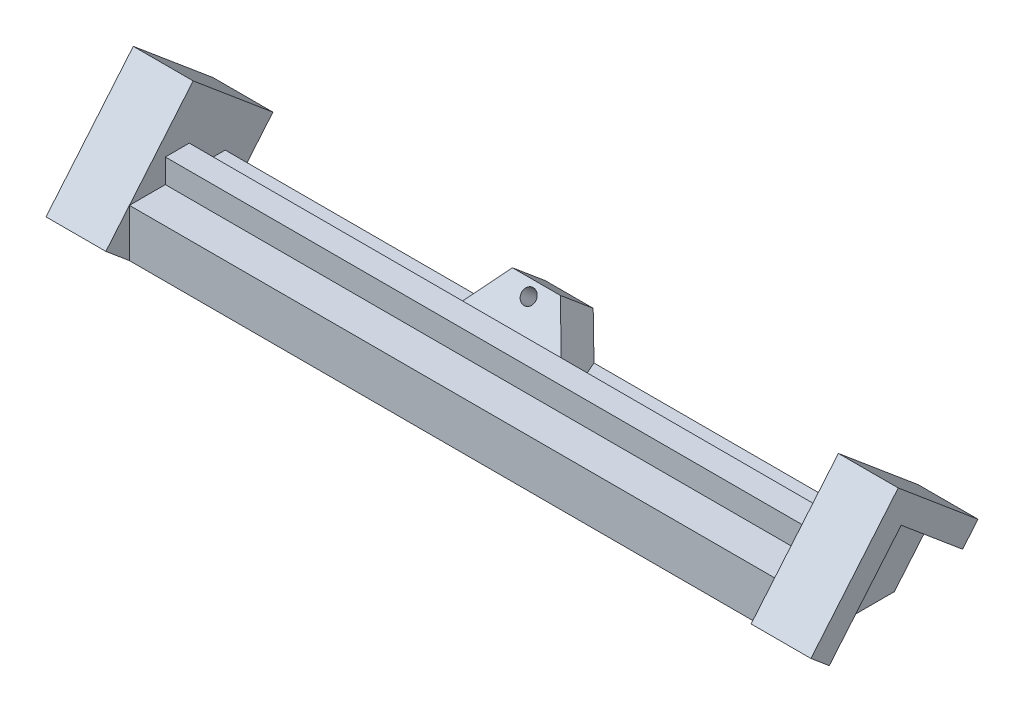
SolidWorks part; units mm, degrees
ref_plane "Front Plane" through (0, 0, 0) normal (0, 0, 1) x (1, 0, 0)
ref_plane "Top Plane" through (0, 0, 0) normal (0, 1, 0) x (1, 0, 0)
ref_plane "Right Plane" through (0, 0, 0) normal (1, 0, 0) x (0, 0, -1)
sketch "Sketch1" plane through (0, 0, 0) normal (0, 1, 0) x (1, 0, 0)
  line L1 (0, 0) -> (183.8325, 0)
  line L2 (0, 0) -> (0, 25.4)
  line L3 (0, 25.4) -> (183.8325, 25.4)
  line L4 (183.8325, 0) -> (183.8325, 25.4)
  dimension "D1" = 183.8325
  dimension "D2" = 25.4
extrude "Boss-Extrude1" add sketch "Sketch1" along normal blind 12.7
ref_plane "Plane1" through (91.9162, 0, 0) normal (1, 0, 0) x (0, 0, -1)
sketch "Sketch2" plane through (0, 0, 0) normal (-1, 0, 0) x (0, 0, 1)
  line L0 (0, 12.7) -> (0, 0) construction
  line L1 (-3.175, 6.35) -> (-3.175, 12.7) construction
  line L2 (-25.4, 12.7) -> (0, 12.7) construction
  line L3 (-3.175, 6.35) -> (-3.175, 0) construction
  line L4 (-25.4, 0) -> (0, 0) construction
  circle A0 centre (-3.175, 6.35) radius 1.905
  dimension "D2" = 3.81
  dimension "D1" = 3.175
extrude "Cut-Extrude1" cut sketch "Sketch2" against normal blind 12.7
sketch "Sketch3" plane through (183.8325, 0, 0) normal (1, 0, 0) x (0, 0, -1)
  line L0 (25.4, 0) -> (38.0577, 15.0849)
  line L1 (38.0577, 15.0849) -> (16.8988, 32.8393)
  line L2 (16.8988, 32.8393) -> (-6.2535, 5.2473)
  line L4 (36.6353, 7.989) -> (18.8976, 22.8728) construction
  line L5 (0, 0) -> (25.4, 0)
  line L13 (0, 0) -> (-6.2535, 5.2473)
  dimension "D2" = 6.35
extrude "Boss-Extrude2" add sketch "Sketch3" against normal blind 6.35
sketch "Sketch4" plane through (183.8325, 0, 0) normal (1, 0, 0) x (0, 0, -1)
  line L0 (-6.2535, 5.2473) -> (16.8988, 32.8393)
  line L1 (16.8988, 32.8393) -> (38.0577, 15.0849)
  line L9 (16.8988, 32.8393) -> (-6.2535, 5.2473) construction
  line L10 (-6.2535, 5.2473) -> (-1.3891, 1.1656)
  line L11 (-1.3891, 1.1656) -> (17.6815, 23.8932)
  line L12 (17.6815, 23.8932) -> (33.976, 10.2205)
  line L13 (25.4, 0) -> (38.0577, 15.0849) construction
  line L14 (33.976, 10.2205) -> (38.0577, 15.0849)
  line L16 (-6.2535, 5.2473) -> (0, 0) construction
  dimension "D1" = 6.35
  dimension "D2" = 6.35
extrude "Boss-Extrude3" add sketch "Sketch4" along normal blind 9.525 contours L0 L1 L14 L12 L11 L10
mirror "Mirror1" about plane through (91.9162, 0, 0) normal (1, 0, 0) of "Boss-Extrude3", "Boss-Extrude2", "Boss-Extrude1"
sketch "Sketch5" plane through (0, 12.7, 0) normal (0, 1, 0) x (1, 0, 0)
  line L0 (6.35, 38.0577) -> (6.35, 16.8988) construction
  line L1 (6.35, 15.875) -> (177.4825, 15.875)
  line L2 (6.35, 15.875) -> (6.35, 9.525)
  line L3 (6.35, 9.525) -> (177.4825, 9.525)
  line L4 (177.4825, 15.875) -> (177.4825, 9.525)
  line L5 (177.4825, 16.8988) -> (177.4825, 0) construction
  line L6 (91.9162, 9.525) -> (91.9162, 0) construction
  line L7 (6.35, 0) -> (177.4825, 0) construction
  line L8 (91.9162, 15.875) -> (91.9162, 25.4) construction
  line L9 (177.4825, 25.4) -> (6.35, 25.4) construction
  dimension "D1" = 6.35
extrude "Boss-Extrude4" add sketch "Sketch5" along normal blind 6.35 contours L1 L4 L3 L2
ref_plane "Plane2" through (0, 0.0541, 0.0645) normal (0, 0.6428, 0.766) x (1, 0, 0)
sketch "Sketch8" plane through (0, 0.0541, 0.0645) normal (0, 0.6428, 0.766) x (1, 0, 0)
  line L0 (72.8662, 15.8513) -> (85.5662, 34.9013)
  line L1 (6.35, 15.8513) -> (177.4825, 15.8513) construction
  line L2 (85.5662, 34.9013) -> (98.2662, 34.9013)
  line L3 (98.2662, 34.9013) -> (110.9662, 15.8513)
  line L4 (110.9662, 15.8513) -> (72.8662, 15.8513)
  line L6 (72.8662, 15.8513) -> (6.35, 15.8513) construction
  line L7 (110.9662, 15.8513) -> (177.4825, 15.8513) construction
  dimension "D1" = 38.1
  dimension "D2" = 12.7
  dimension "D3" = 19.05
extrude "Boss-Extrude6" add sketch "Sketch8" against normal up to vertex (11.3783 mm away) up to point (177.4825, 12.7, -25.4)
sketch "Sketch9" plane through (0, 0.0541, 0.0645) normal (0, 0.6428, 0.766) x (1, 0, 0)
  line L0 (91.9162, 31.7263) -> (83.4496, 31.7263) construction
  line L1 (85.5662, 34.9013) -> (78.8303, 24.7974) construction
  line L2 (91.9162, 31.7263) -> (100.3829, 31.7263) construction
  line L3 (105.0022, 24.7974) -> (98.2662, 34.9013) construction
  line L4 (98.2662, 34.9013) -> (85.5662, 34.9013) construction
  circle A0 centre (91.9162, 31.7263) radius 1.905
  dimension "D1" = 3.81
  dimension "D2" = 3.175
extrude "Cut-Extrude3" cut sketch "Sketch9" against normal through all
